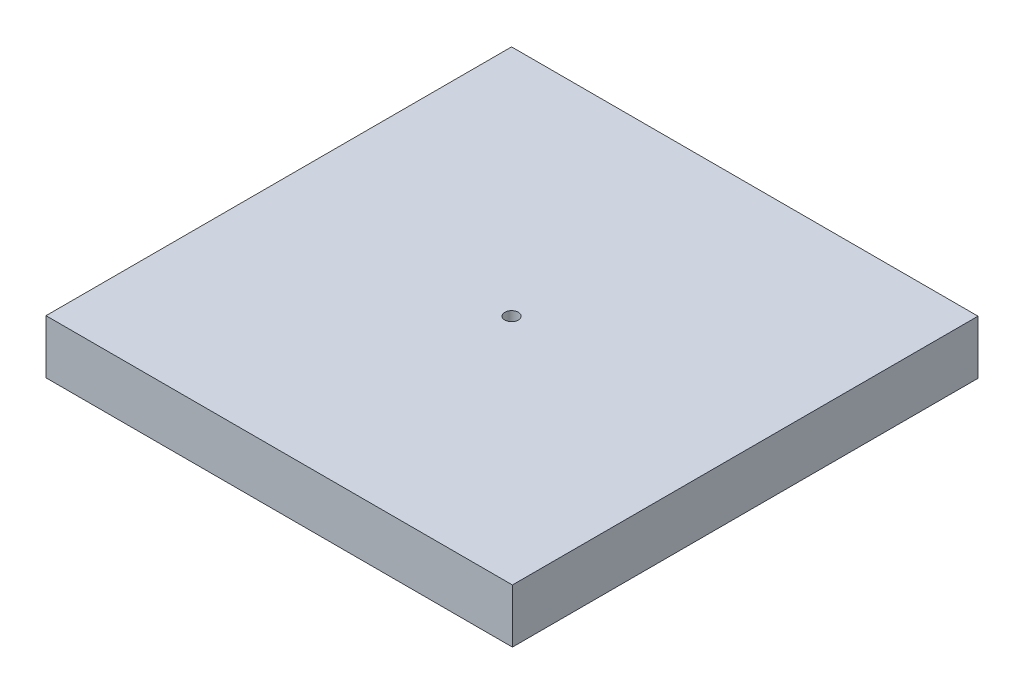
SolidWorks part; units mm, degrees
ref_plane "Front Plane" through (0, 0, 0) normal (0, 0, 1) x (1, 0, 0)
ref_plane "Top Plane" through (0, 0, 0) normal (0, 1, 0) x (1, 0, 0)
ref_plane "Right Plane" through (0, 0, 0) normal (1, 0, 0) x (0, 0, -1)
sketch "Sketch4" plane through (0, 0, 0) normal (0, 1, 0) x (1, 0, 0)
  line L1 (61.7729, 131.481) -> (281.7729, 131.481)
  line L2 (61.7729, 131.481) -> (61.7729, -88.519)
  line L3 (61.7729, -88.519) -> (281.7729, -88.519)
  line L4 (281.7729, 131.481) -> (281.7729, -88.519)
  dimension "D1" = 220
extrude "Boss-Extrude2" add sketch "Sketch4" along normal blind 25.4
sketch "Sketch5" plane through (0, 25.4, 0) normal (0, 1, 0) x (1, 0, 0)
  circle A0 centre (171.7729, 21.481) radius 3.2
extrude "Cut-Extrude1" cut sketch "Sketch5" against normal blind 25.4
sketch "Sketch13" plane through (0, 0, 88.519) normal (0, 0, 1) x (1, 0, 0)
  line L1 (61.7729, 25.4) -> (281.7729, 25.4)
  line L2 (61.7729, 25.4) -> (61.7729, 0)
  line L3 (61.7729, 0) -> (281.7729, 0)
  line L4 (281.7729, 25.4) -> (281.7729, 0)
  dimension "D1" = 25.4
  dimension "D2" = 220
extrude "Boss-Extrude3" add sketch "Sketch13" along normal blind 25
sketch "Sketch14" plane through (0, 0, 113.519) normal (0, 0, 1) x (1, 0, 0)
  line L1 (61.7729, 25.4) -> (281.7729, 25.4)
  line L2 (61.7729, 25.4) -> (61.7729, 0)
  line L3 (61.7729, 0) -> (281.7729, 0)
  line L4 (281.7729, 25.4) -> (281.7729, 0)
extrude "Cut-Extrude2" cut sketch "Sketch14" against normal blind 25.4
